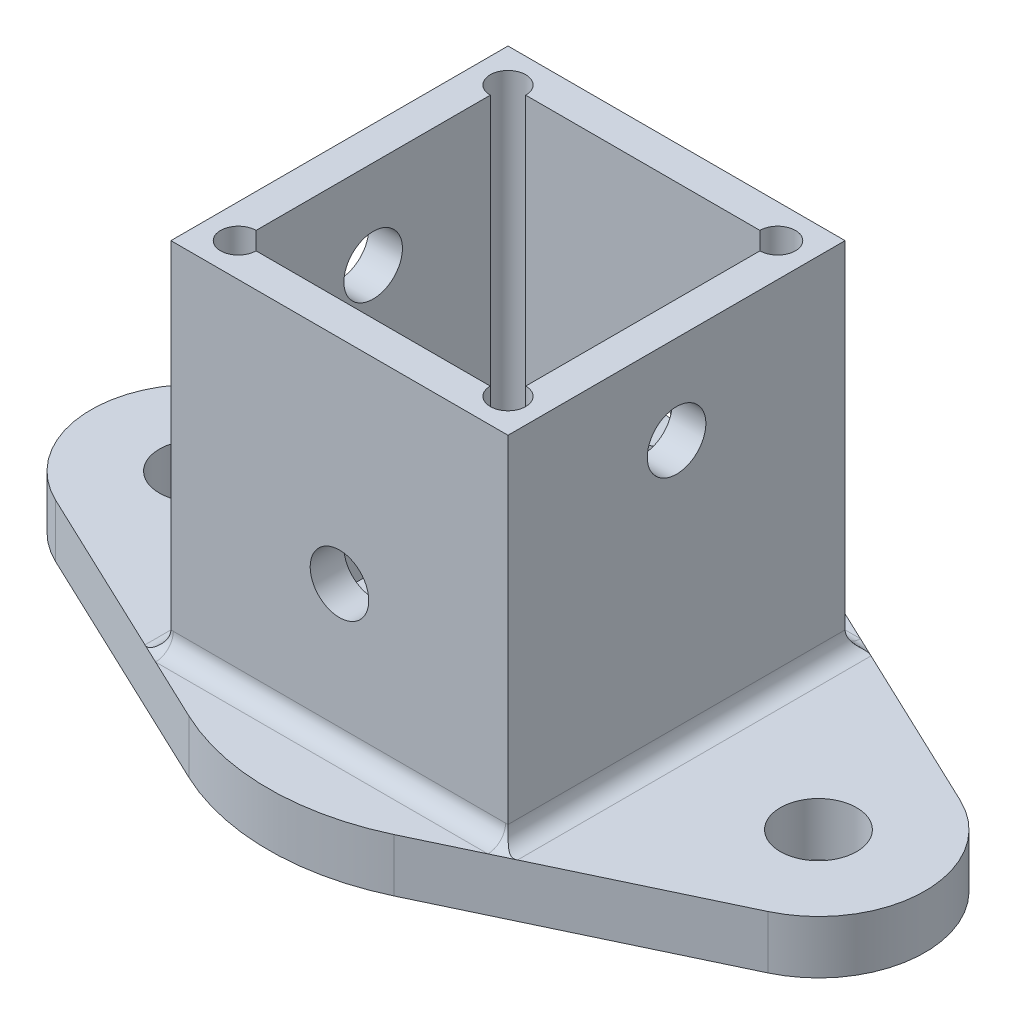
SolidWorks part; units mm, degrees
material "ABS"
ref_plane "前视基准面" through (0, 0, 0) normal (0, 0, 1) x (1, 0, 0)
ref_plane "上视基准面" through (0, 0, 0) normal (0, 1, 0) x (1, 0, 0)
ref_plane "右视基准面" through (0, 0, 0) normal (1, 0, 0) x (0, 0, -1)
other "Configuration Table"
sketch "草图1" plane through (0, 0, 0) normal (0, 1, 0) x (1, 0, 0)
  line L0 (-40.5759, 0) -> (40.5265, 0) construction
  line L1 (0, 33.3733) -> (0, -29.1801) construction
  line L2 (-20.0714, 5.421) -> (-5.7857, 12.1974)
  line L3 (20.0714, 5.421) -> (5.7857, 12.1974)
  line L4 (20.0714, -5.421) -> (5.7857, -12.1974)
  line L5 (-20.0714, -5.421) -> (-5.7857, -12.1974)
  circle A0 centre (0, 0) radius 13.5 construction
  circle A1 centre (-17.5, 0) radius 2.15
  circle A2 centre (17.5, 0) radius 2.15
  arc A3 (-20.0714, 5.421) -> (-19.5517, -5.6383) centre (-17.5, 0) ccw
  arc A4 (20.0714, 5.421) -> (19.5517, -5.6383) centre (17.5, 0) cw
  arc A5 (5.7857, 12.1974) -> (-5.7857, 12.1974) centre (0, 0) ccw
  arc A6 (-5.7857, -12.1974) -> (5.7857, -12.1974) centre (0, 0) ccw
  dimension "D1" = 27
  dimension "D2" = 35
  dimension "D3" = 4.3
  dimension "D4" = 6
extrude "凸台-拉伸1" add sketch "草图1" along normal blind 3 contours L5 A6 L4 A4 L3 A5 L2 A3 A2 A1 region at (0, 0, 0)
sketch "草图2" plane through (0, 3, 0) normal (0, 1, 0) x (1, 0, 0)
  line L1 (-9.5, -9.5) -> (9.5, -9.5)
  line L2 (-9.5, -9.5) -> (-9.5, 9.5)
  line L3 (-9.5, 9.5) -> (9.5, 9.5)
  line L4 (9.5, -9.5) -> (9.5, 9.5)
  line L5 (-9.5, -9.5) -> (9.5, 9.5) construction
  line L6 (-9.5, 9.5) -> (9.5, -9.5) construction
  line L7 (-7.6, -7.6) -> (7.6, -7.6)
  line L8 (-7.6, -7.6) -> (-7.6, 7.6)
  line L9 (-7.6, 7.6) -> (7.6, 7.6)
  line L10 (7.6, -7.6) -> (7.6, 7.6)
  line L11 (-7.6, -7.6) -> (7.6, 7.6) construction
  line L12 (-7.6, 7.6) -> (7.6, -7.6) construction
  point P0 (0, 0)
  point P6 (0, 0)
  dimension "D1" = 19
  dimension "D2" = 15.2
extrude "凸台-拉伸2" add sketch "草图2" along normal blind 20
sketch "草图3" plane through (0, 23, 0) normal (0, 1, 0) x (1, 0, 0)
  circle A0 centre (-7.6, 7.6) radius 1
  circle A1 centre (7.6, 7.6) radius 1
  circle A2 centre (7.6, -7.6) radius 1
  circle A3 centre (-7.6, -7.6) radius 1
  dimension "D1" = 2
extrude "切除-拉伸1" cut sketch "草图3" against normal up to surface (20 mm away) and the other way through all up to face at (0, 3, 0)
fillet "圆角4" radius 1 4 edges at (-9.5, 3, 0) (0, 3, -9.5) (9.5, 3, 0) (0, 3, 9.5)
sketch "草图4" plane through (0, 0, -9.5) normal (0, 0, -1) x (-1, 0, 0)
  line L0 (0, 27.9062) -> (0, -6.4342) construction
  line L1 (-9.3641, 4) -> (9.3641, 4) construction
  circle A0 centre (0, 11) radius 1.65
  dimension "D1" = 3.3
  dimension "D2" = 7
extrude "切除-拉伸2" cut sketch "草图4" against normal through all both and the other way through all
sketch "草图5" plane through (9.5, 0, 0) normal (1, 0, 0) x (0, 0, -1)
  line L0 (0, 23.7104) -> (0, -0.9564) construction
  line L1 (-9.5, 4) -> (9.5, 4) construction
  circle A0 centre (0, 18) radius 1.65
  dimension "D1" = 3.3
  dimension "D2" = 14
extrude "切除-拉伸3" cut sketch "草图5" against normal through all both and the other way through all
